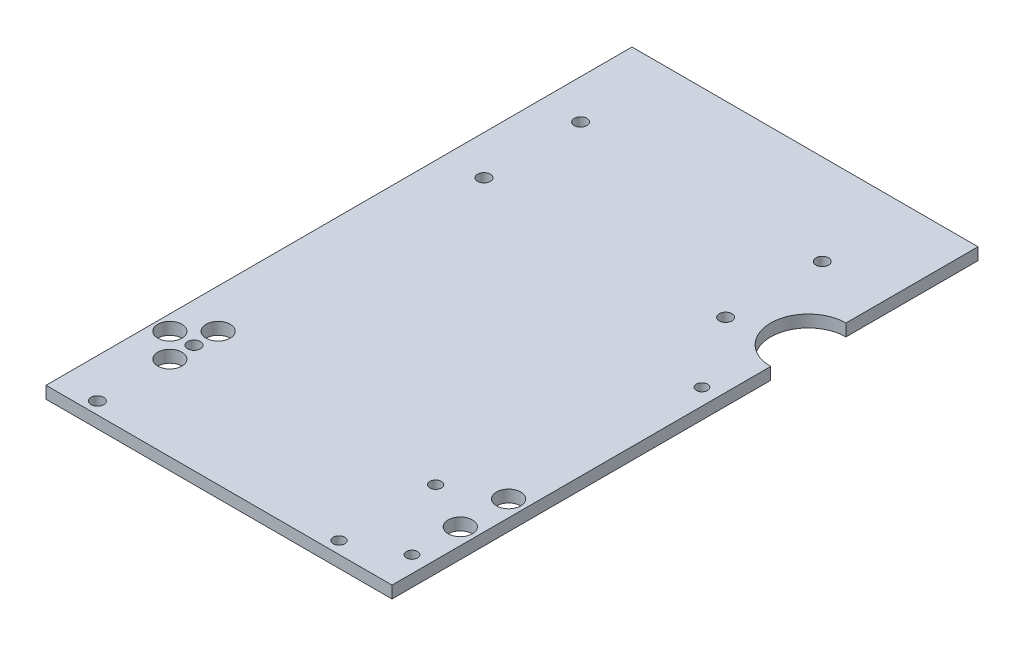
SolidWorks part; units mm, degrees
material "Acrylic (Medium-high impact)"
ref_plane "Front" through (0, 0, 0) normal (0, 0, 1) x (1, 0, 0)
ref_plane "Top" through (0, 0, 0) normal (0, 1, 0) x (1, 0, 0)
ref_plane "Right" through (0, 0, 0) normal (1, 0, 0) x (0, 0, -1)
ref_axis "side-side" through (80.9, 0, 0) along (-1, 0, 0)
ref_axis "up-down" through (0, 50, 0) along (0, -1, 0)
ref_axis "front-back" through (0, 0, -80.9) along (0, 0, 1)
sketch "Sketch1" plane through (0, 0, 0) normal (0, 1, 0) x (1, 0, 0)
  line L0 (-25.44, 136.2407) -> (-25.44, -151.7593) construction
  line L1 (-141, -139.7593) -> (-26.44, -139.7593)
  line L2 (-141, -139.7593) -> (-141, 54.2407)
  line L3 (-141, 54.2407) -> (-26.44, 54.2407)
  line L4 (-26.44, -139.7593) -> (-26.44, -14.4008)
  line L5 (-142, 136.2407) -> (-142, -258.9792) construction
  line L7 (-56, 44.2407) -> (-48, 44.2407) construction
  line L8 (-144, -119.7593) -> (144, -119.7593) construction
  line L9 (-26.44, 10.5343) -> (-26.44, 54.2407)
  circle A0 centre (-31.84, -31.7593) radius 1.85 construction
  circle A1 centre (-31.84, -31.7593) radius 1.85
  circle A2 centre (-31.84, -127.7593) radius 1.85 construction
  circle A3 centre (-31.84, -127.7593) radius 1.85
  circle A5 centre (-48, -135.7593) radius 1.905
  circle A6 centre (-48, -135.7593) radius 2.1 construction
  circle A7 centre (-48, -103.7593) radius 1.905
  circle A8 centre (-48, -103.7593) radius 2.1 construction
  circle A9 centre (-128, -135.7593) radius 2.1 construction
  circle A10 centre (-128, -135.7593) radius 2.1
  circle A11 centre (-128, -103.7593) radius 2.1 construction
  circle A12 centre (-128, -103.7593) radius 2.1
  circle A13 centre (-136, -103.7593) radius 4
  circle A14 centre (-128, -103.7593) radius 4 construction
  circle A15 centre (-136, -103.7593) radius 1.85 construction
  circle A16 centre (-128, -95.7593) radius 4
  circle A17 centre (-128, -95.7593) radius 1.85 construction
  circle A18 centre (-128, -111.7593) radius 4
  circle A19 centre (-128, -111.7593) radius 1.85 construction
  circle A20 centre (-128, -7.7593) radius 2.1 construction
  circle A21 centre (-128, -7.7593) radius 2.1
  circle A22 centre (-128, 24.2407) radius 2.1 construction
  circle A23 centre (-128, 24.2407) radius 2.1
  circle A24 centre (-48, -7.7593) radius 2.1 construction
  circle A25 centre (-48, -7.7593) radius 2.1
  circle A26 centre (-48, 24.2407) radius 2.1 construction
  circle A27 centre (-48, 24.2407) radius 2.1
  circle A28 centre (-31.84, -111.7593) radius 4
  circle A29 centre (-31.84, -95.7593) radius 4
  arc A30 (-26.44, 10.5343) -> (-26.44, -14.4008) centre (-26.44, -1.9333) ccw
  circle A31 centre (-16, -103.7593) radius 4 construction
  dimension "D5" = 3.81
  dimension "D1" = 1
  dimension "D2" = 1
  dimension "D3" = 20
  dimension "D4" = 10
extrude "Boss-Extrude1" add sketch "Sketch1" against normal blind 4
